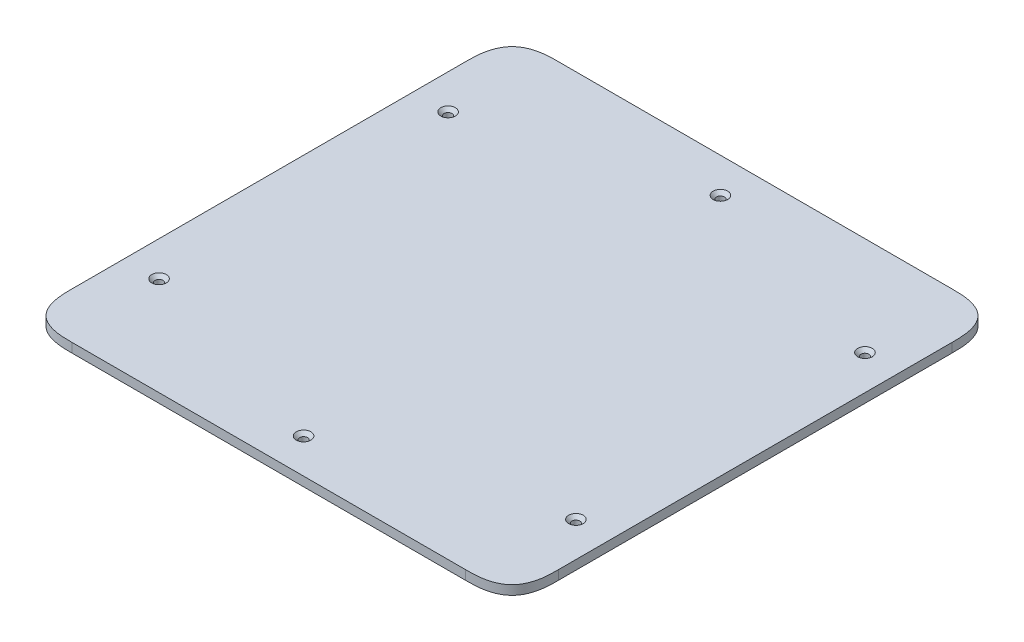
SolidWorks part; units mm, degrees
ref_plane "Спереди" through (0, 0, 0) normal (0, 0, 1) x (1, 0, 0)
ref_plane "Сверху" through (0, 0, 0) normal (0, 1, 0) x (1, 0, 0)
ref_plane "Справа" through (0, 0, 0) normal (1, 0, 0) x (0, 0, -1)
sketch "Эскиз1" plane through (0, 0, 0) normal (0, 1, 0) x (1, 0, 0)
  line L0 (105, -85) -> (105, 85) construction
  line L1 (-85, -105) -> (85, -105) construction
  line L2 (-105, -85) -> (-105, 85) construction
  line L3 (-85, 105) -> (85, 105) construction
  line L4 (105, -85) -> (105, 85)
  line L5 (-85, -105) -> (85, -105)
  line L6 (-105, -85) -> (-105, 85)
  line L7 (-85, 105) -> (85, 105)
  spline S0 degree 2 poles (87.7075, -914.8503) (105.4682, 60.1336) (104.9873, 87.0793) (104.9672, 88.2064) (104.906, 89.1526) (104.7612, 91.3925) (104.3447, 93.2636) (103.3156, 97.8875) (100.6213, 100.5918) (97.9211, 103.3021) (93.2885, 104.3392) (91.4177, 104.758) (89.1768, 104.9045) (88.2251, 104.9667) (87.0892, 104.9871) (60.1244, 105.4731) (-914.8432, 87.5821) knots -2.308504 -2.308504 -2.308504 0.0625 0.0625 0.125 0.125 0.25 0.25 0.5 0.5 0.75 0.75 0.875 0.875 0.9375 0.9375 3.300825 3.300825 3.300825 only from (105, 85) to (85, 105) construction
  spline S1 degree 2 poles (-914.8503, -87.7075) (60.1336, -105.4682) (87.0793, -104.9873) (88.2064, -104.9672) (89.1526, -104.906) (91.3925, -104.7612) (93.2636, -104.3447) (97.8875, -103.3156) (100.5918, -100.6213) (103.3021, -97.9211) (104.3392, -93.2885) (104.758, -91.4177) (104.9045, -89.1768) (104.9667, -88.2251) (104.9871, -87.0892) (105.4731, -60.1244) (87.5821, 914.8432) knots -2.308504 -2.308504 -2.308504 0.0625 0.0625 0.125 0.125 0.25 0.25 0.5 0.5 0.75 0.75 0.875 0.875 0.9375 0.9375 3.300825 3.300825 3.300825 only from (85, -105) to (105, -85) construction
  spline S2 degree 2 poles (-87.7075, 914.8503) (-105.4682, -60.1336) (-104.9873, -87.0793) (-104.9672, -88.2064) (-104.906, -89.1526) (-104.7612, -91.3925) (-104.3447, -93.2636) (-103.3156, -97.8875) (-100.6213, -100.5918) (-97.9211, -103.3021) (-93.2885, -104.3392) (-91.4177, -104.758) (-89.1768, -104.9045) (-88.2251, -104.9667) (-87.0892, -104.9871) (-60.1244, -105.4731) (914.8432, -87.5821) knots -2.308504 -2.308504 -2.308504 0.0625 0.0625 0.125 0.125 0.25 0.25 0.5 0.5 0.75 0.75 0.875 0.875 0.9375 0.9375 3.300825 3.300825 3.300825 only from (-105, -85) to (-85, -105) construction
  spline S3 degree 2 poles (914.8503, 87.7075) (-60.1336, 105.4682) (-87.0793, 104.9873) (-88.2064, 104.9672) (-89.1526, 104.906) (-91.3925, 104.7612) (-93.2636, 104.3447) (-97.8875, 103.3156) (-100.5918, 100.6213) (-103.3021, 97.9211) (-104.3392, 93.2885) (-104.758, 91.4177) (-104.9045, 89.1768) (-104.9667, 88.2251) (-104.9871, 87.0892) (-105.4731, 60.1244) (-87.5821, -914.8432) knots -2.308504 -2.308504 -2.308504 0.0625 0.0625 0.125 0.125 0.25 0.25 0.5 0.5 0.75 0.75 0.875 0.875 0.9375 0.9375 3.300825 3.300825 3.300825 only from (-85, 105) to (-105, 85) construction
  spline S4 degree 2 poles (105, 85) (105, 86.369) (104.9873, 87.0793) (104.9672, 88.2064) (104.906, 89.1526) (104.7612, 91.3925) (104.3447, 93.2636) (103.3156, 97.8875) (100.6213, 100.5918) (97.9211, 103.3021) (93.2885, 104.3392) (91.4177, 104.758) (89.1768, 104.9045) (88.2251, 104.9667) (87.0892, 104.9871) (86.3761, 105) (85, 105) knots 0 0 0 0.0625 0.0625 0.125 0.125 0.25 0.25 0.5 0.5 0.75 0.75 0.875 0.875 0.9375 0.9375 1 1 1
  spline S5 degree 2 poles (85, -105) (86.369, -105) (87.0793, -104.9873) (88.2064, -104.9672) (89.1526, -104.906) (91.3925, -104.7612) (93.2636, -104.3447) (97.8875, -103.3156) (100.5918, -100.6213) (103.3021, -97.9211) (104.3392, -93.2885) (104.758, -91.4177) (104.9045, -89.1768) (104.9667, -88.2251) (104.9871, -87.0892) (105, -86.3761) (105, -85) knots 0 0 0 0.0625 0.0625 0.125 0.125 0.25 0.25 0.5 0.5 0.75 0.75 0.875 0.875 0.9375 0.9375 1 1 1
  spline S6 degree 2 poles (-105, -85) (-105, -86.369) (-104.9873, -87.0793) (-104.9672, -88.2064) (-104.906, -89.1526) (-104.7612, -91.3925) (-104.3447, -93.2636) (-103.3156, -97.8875) (-100.6213, -100.5918) (-97.9211, -103.3021) (-93.2885, -104.3392) (-91.4177, -104.758) (-89.1768, -104.9045) (-88.2251, -104.9667) (-87.0892, -104.9871) (-86.3761, -105) (-85, -105) knots 0 0 0 0.0625 0.0625 0.125 0.125 0.25 0.25 0.5 0.5 0.75 0.75 0.875 0.875 0.9375 0.9375 1 1 1
  spline S7 degree 2 poles (-85, 105) (-86.369, 105) (-87.0793, 104.9873) (-88.2064, 104.9672) (-89.1526, 104.906) (-91.3925, 104.7612) (-93.2636, 104.3447) (-97.8875, 103.3156) (-100.5918, 100.6213) (-103.3021, 97.9211) (-104.3392, 93.2885) (-104.758, 91.4177) (-104.9045, 89.1768) (-104.9667, 88.2251) (-104.9871, 87.0892) (-105, 86.3761) (-105, 85) knots 0 0 0 0.0625 0.0625 0.125 0.125 0.25 0.25 0.5 0.5 0.75 0.75 0.875 0.875 0.9375 0.9375 1 1 1
extrude "Бобышка-Вытянуть1" add sketch "Эскиз1" along normal blind 4
hole_wizard "Зенковка для винта с полупотайной головкой M32" positions "Эскиз10" profile "Эскиз11" countersink size "M3" standard "DIN" end condition through all
sketch "Эскиз10" plane through (0, 4, 0) normal (0, 1, 0) x (1, 0, 0)
  point P0 (90, -62.4)
  point P3 (90, 62.4)
  point P6 (0, -90)
  point P11 (-90, -62.4)
  point P19 (0, 90)
  point P22 (-90, 62.4)
sketch "Эскиз11" plane through (90, 4, 62.4) normal (1, 0, 0) x (0, 0, 1)
  line L0 (0, 0) -> (0, 4.05)
  line L1 (0, 4.05) -> (1.7, 4.05)
  line L2 (1.7, 4.05) -> (1.7, 1.45)
  line L3 (1.7, 1.45) -> (3.15, 0)
  line L5 (3.15, 0) -> (0, 0)
  line L6 (-1.7, 1.45) -> (-3.15, 0) construction
  line L11 (0, -6.35) -> (0, 107.95) construction
  dimension "Диаметр сквозного отверстия" = 3.4
  dimension "Глубина сквозного отверстия" = 4.05
  dimension "Диаметр передней зенковки" = 6.3
  dimension "Угол передней зенковки" = 90
